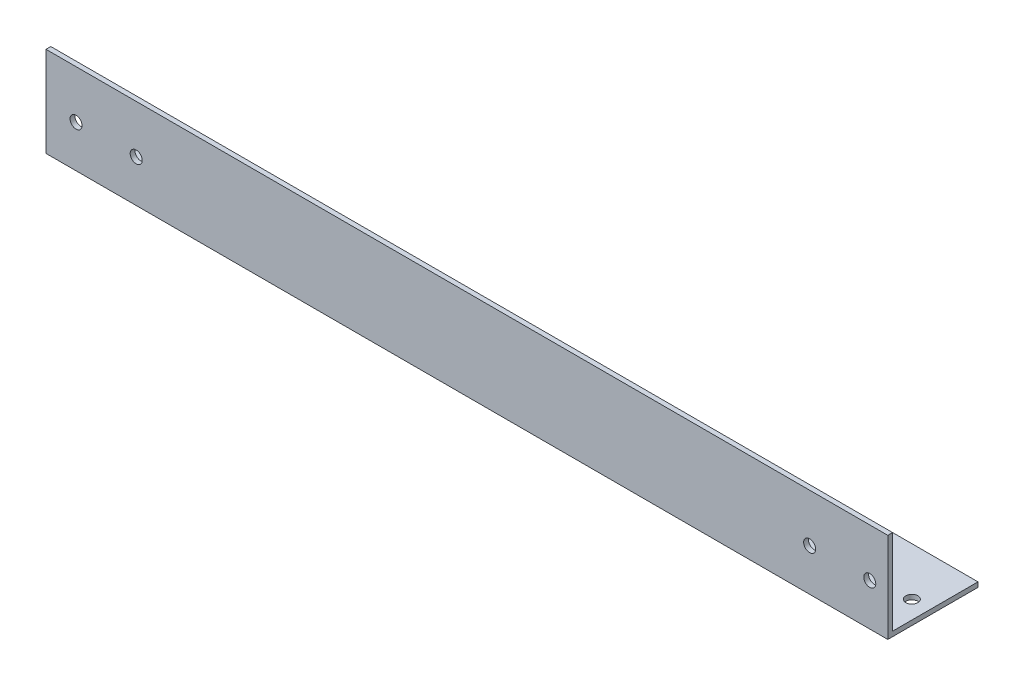
SolidWorks part; units mm, degrees
ref_plane "Спереди" through (0, 0, 0) normal (0, 0, 1) x (1, 0, 0)
ref_plane "Сверху" through (0, 0, 0) normal (0, 1, 0) x (1, 0, 0)
ref_plane "Справа" through (0, 0, 0) normal (1, 0, 0) x (0, 0, -1)
sketch "Эскиз1" plane through (0, 0, 0) normal (1, 0, 0) x (0, 0, -1)
  line L0 (0, 0) -> (0, 75)
  line L1 (0, 0) -> (75, 0)
extrude "Вытянуть-Тонкостенный1" add sketch "Эскиз1" along normal blind 700 thin thin type one direction reverse wall 4
sketch "Эскиз2" plane through (0, 0, 0) normal (0, 0, 1) x (1, 0, 0)
  circle A0 centre (25, 35) radius 5
  circle A1 centre (75, 35) radius 5
  circle A6 centre (635, 35) radius 5
  circle A7 centre (685, 35) radius 5
  dimension "D1" = 2
extrude "Вырез-Вытянуть1" cut sketch "Эскиз2" against normal blind 10
sketch "Эскиз3" plane through (0, 0, 0) normal (0, -1, 0) x (1, 0, 0)
  circle A0 centre (25, -35) radius 5
  circle A1 centre (75, -35) radius 5
  circle A6 centre (635, -35) radius 5
  circle A7 centre (685, -35) radius 5
  dimension "D1" = 2
extrude "Вырез-Вытянуть2" cut sketch "Эскиз3" against normal blind 10
